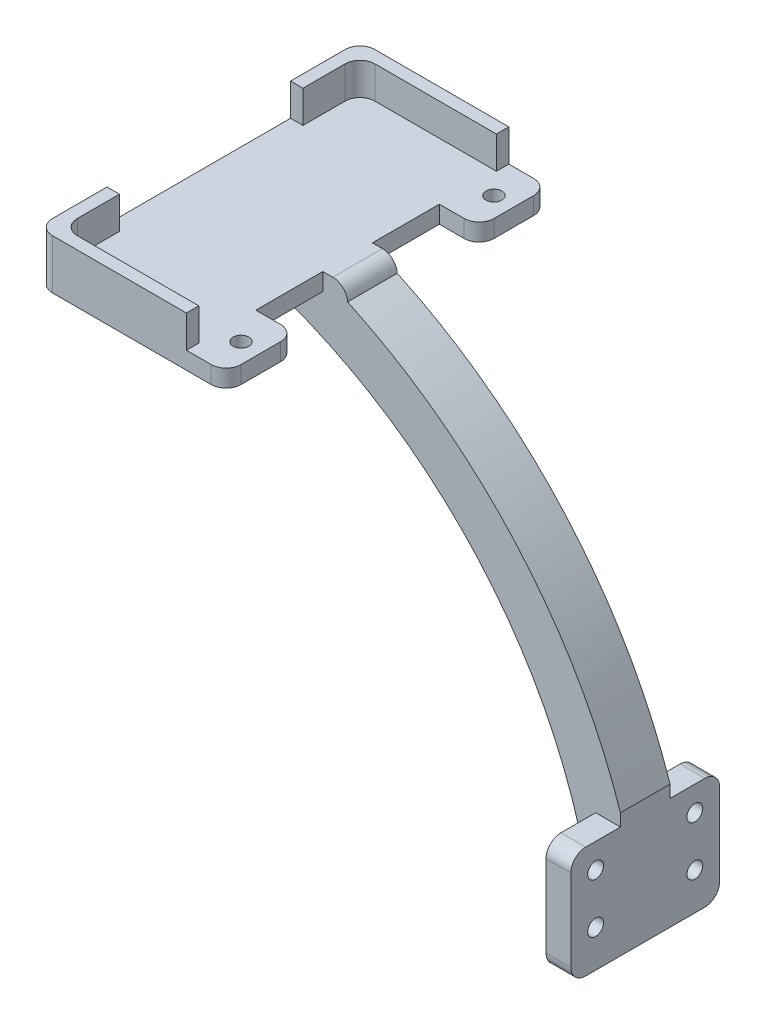
SolidWorks part; units mm, degrees
ref_plane "Plan de face" through (0, 0, 0) normal (0, 0, 1) x (1, 0, 0)
ref_plane "Plan de dessus" through (0, 0, 0) normal (0, 1, 0) x (1, 0, 0)
ref_plane "Plan de droite" through (0, 0, 0) normal (1, 0, 0) x (0, 0, -1)
sketch "Esquisse1" plane through (0, 0, 0) normal (0, 0, 1) x (1, 0, 0)
  line L1 (-15, -5) -> (15, -5)
  line L2 (-15, -5) -> (-15, 5)
  line L3 (-15, 5) -> (15, 5)
  line L4 (15, -5) -> (15, 5)
  line L5 (-15, -5) -> (15, 5) construction
  line L6 (-15, 5) -> (15, -5) construction
  point P0 (0, 0)
  dimension "D1" = 30
  dimension "D2" = 10
extrude "Boss.-Extru.1" add sketch "Esquisse1" along normal blind 65
sketch "Esquisse2" plane through (0, 5, 0) normal (0, 1, 0) x (1, 0, 0)
  line L0 (-15, -65) -> (-15, 0) construction
  line L1 (-15, -14) -> (-12.5, -14)
  line L2 (-15, -14) -> (-15, -51)
  line L3 (-15, -51) -> (-12.5, -51)
  line L5 (15, -65) -> (15, 0) construction
  line L6 (-12.5, -51) -> (-12.5, -62.5)
  line L7 (15, -2.5) -> (-12.5, -2.5)
  line L8 (15, -2.5) -> (15, -62.5)
  line L9 (15, -62.5) -> (-12.5, -62.5)
  line L10 (-12.5, -2.5) -> (-12.5, -14)
  point P6 (-15, -32.5)
  dimension "D1" = 37
  dimension "D2" = 2.5
  dimension "D3" = 60
extrude "Enlèv. mat.-Extru.1" cut sketch "Esquisse2" against normal blind 6.5
sketch "Esquisse3" plane through (15, 0, 0) normal (1, 0, 0) x (0, 0, -1)
  line L0 (-62.5, -1.5) -> (-2.5, -1.5) construction
  line L1 (-65, -5) -> (-51, -5)
  line L2 (-65, -5) -> (-65, -1.5)
  line L3 (-65, -1.5) -> (-51, -1.5)
  line L4 (-51, -5) -> (-51, -1.5)
  line L5 (-51, -1.5) -> (-62.5, -1.5) construction
  line L7 (-14, -1.5) -> (0, -1.5)
  line L8 (-14, -1.5) -> (-14, -5)
  line L9 (-14, -5) -> (0, -5)
  line L10 (0, -1.5) -> (0, -5)
extrude "Boss.-Extru.2" add sketch "Esquisse3" along normal blind 8
sketch "Esquisse4" plane through (0, -1.5, 0) normal (0, 1, 0) x (1, 0, 0)
  line L0 (19, -7) -> (19, -58) construction
  line L1 (-15, -14) -> (-15, -51) construction
  line L2 (23, 0) -> (23, -14) construction
  line L3 (23, 0) -> (15, 0) construction
  circle A0 centre (19, -7) radius 1.6
  circle A1 centre (19, -58) radius 1.6
  point P2 (19, -32.5)
  point P5 (-15, -32.5)
  point P8 (23, -7)
  point P11 (19, 0)
  dimension "D1" = 3.2
extrude "Enlèv. mat.-Extru.2" cut sketch "Esquisse4" against normal blind 4
fillet "Congé1" radius 3 6 edges at (-15, 0, 0) (-15, 0, 65) (23, -3.25, 65) (23, -3.25, 0) (23, -3.25, 14) (23, -3.25, 51)
sketch "Esquisse5" plane through (0, 0, 65) normal (0, 0, 1) x (1, 0, 0)
  line L0 (-15, -5) -> (75, -5) construction
  line L1 (75, -5) -> (75, -66) construction
  line L3 (75, -66) -> (70, -66) construction
  line L4 (75, -66) -> (75, -91)
  line L5 (75, -91) -> (70, -91)
  line L6 (70, -66) -> (70, -91) construction
  line L7 (20, -1.5) -> (15, -1.5) construction
  line L8 (13.3674, -1.5) -> (15, -1.5)
  line L9 (15, -1.5) -> (15, 5) construction
  line L10 (15, -1.5) -> (-15, -5)
  circle A0 centre (-24.0415, -98.9422) radius 94.3763 construction
  circle A1 centre (-24.0415, -98.9422) radius 104.3763 construction
  arc A2 (70, -91) -> (-15, -5) centre (-24.0415, -98.9422) ccw
  arc A3 (75, -66) -> (13.3674, -1.5) centre (-24.0415, -98.9422) ccw
  line M4 (-12, 5) -> (-12, -5)
  line M5 (-12, -5) -> (20, -5)
  line M6 (20, -5) -> (20, -1.5)
  dimension "D5" = 10
  dimension "D1" = 90
  dimension "D2" = 61
  dimension "D3" = 5
  dimension "D4" = 25
extrude "Boss.-Extru.3" add sketch "Esquisse5" against normal blind 5 and the other way blind 5 from offset 32.5 contours L4 A3 L10 A2 L5 M6 M5 M4 region at (73.7504, -78.5, 65) offset against normal yes
sketch "Esquisse6" plane through (0, -5, 0) normal (0, 1, 0) x (1, 0, 0)
  line L1 (20, -27.5) -> (15, -27.5)
  line L2 (20, -27.5) -> (20, -37.5)
  line L3 (20, -37.5) -> (15, -37.5)
  line L4 (15, -27.5) -> (15, -37.5)
extrude "Boss.-Extru.4" add sketch "Esquisse6" along normal blind 3.5
sketch "Esquisse7" plane through (75, 0, 0) normal (1, 0, 0) x (0, 0, -1)
  line L0 (-37.5, -66) -> (-27.5, -66) construction
  line L1 (-42.5, -83.5) -> (-22.5, -83.5) construction
  line L2 (-42.5, -83.5) -> (-42.5, -73.5) construction
  line L3 (-42.5, -73.5) -> (-22.5, -73.5) construction
  line L4 (-22.5, -83.5) -> (-22.5, -73.5) construction
  line L5 (-42.5, -83.5) -> (-22.5, -73.5) construction
  line L6 (-42.5, -73.5) -> (-22.5, -83.5) construction
  line L7 (-37.5, -91) -> (-27.5, -91) construction
  line L9 (-47.5, -91) -> (-17.5, -91)
  line L10 (-47.5, -91) -> (-47.5, -68.5)
  line L11 (-47.5, -68.5) -> (-17.5, -68.5)
  line L12 (-17.5, -91) -> (-17.5, -68.5)
  circle A0 centre (-42.5, -73.5) radius 1.6
  circle A1 centre (-22.5, -73.5) radius 1.6
  circle A2 centre (-22.5, -83.5) radius 1.6
  circle A3 centre (-42.5, -83.5) radius 1.6
  point P0 (-32.5, -78.5)
  point P8 (-32.5, -66)
  point P18 (-32.5, -91)
  dimension "D3" = 3.2
  dimension "D1" = 20
  dimension "D2" = 10
  dimension "D4" = 7.5
  dimension "D5" = 5
  dimension "D6" = 5
extrude "Boss.-Extru.5" add sketch "Esquisse7" against normal blind 5
sketch "Esquisse8" plane through (70, 0, 0) normal (1, 0, 0) x (0, 0, -1)
  line L1 (-40.8834, -70.7) -> (-44.1166, -70.7)
  line L2 (-44.1166, -70.7) -> (-45.7332, -73.5)
  line L3 (-45.7332, -73.5) -> (-44.1166, -76.3)
  line L4 (-44.1166, -76.3) -> (-40.8834, -76.3)
  line L5 (-40.8834, -76.3) -> (-39.2668, -73.5)
  line L6 (-39.2668, -73.5) -> (-40.8834, -70.7)
  line L7 (-20.8834, -70.7) -> (-24.1166, -70.7)
  line L8 (-24.1166, -70.7) -> (-25.7332, -73.5)
  line L9 (-25.7332, -73.5) -> (-24.1166, -76.3)
  line L10 (-24.1166, -76.3) -> (-20.8834, -76.3)
  line L11 (-20.8834, -76.3) -> (-19.2668, -73.5)
  line L12 (-19.2668, -73.5) -> (-20.8834, -70.7)
  line L13 (-20.8834, -86.3) -> (-19.2668, -83.5)
  line L14 (-19.2668, -83.5) -> (-20.8834, -80.7)
  line L15 (-20.8834, -80.7) -> (-24.1166, -80.7)
  line L16 (-24.1166, -80.7) -> (-25.7332, -83.5)
  line L17 (-25.7332, -83.5) -> (-24.1166, -86.3)
  line L18 (-24.1166, -86.3) -> (-20.8834, -86.3)
  line L19 (-40.8834, -86.3) -> (-39.2668, -83.5)
  line L20 (-39.2668, -83.5) -> (-40.8834, -80.7)
  line L21 (-40.8834, -80.7) -> (-44.1166, -80.7)
  line L22 (-44.1166, -80.7) -> (-45.7332, -83.5)
  line L23 (-45.7332, -83.5) -> (-44.1166, -86.3)
  line L24 (-44.1166, -86.3) -> (-40.8834, -86.3)
  circle A0 centre (-42.5, -73.5) radius 2.8 construction
  circle A1 centre (-22.5, -73.5) radius 2.8 construction
  circle A2 centre (-22.5, -83.5) radius 2.8 construction
  circle A3 centre (-42.5, -83.5) radius 2.8 construction
  dimension "D1" = 5.6
extrude "Enlèv. mat.-Extru.3" cut sketch "Esquisse8" along normal blind 2.5
fillet "Congé2" radius 3 4 edges at (72.5, -91, 17.5) (72.5, -91, 47.5) (72.5, -68.5, 47.5) (72.5, -68.5, 17.5)
fillet "Congé3" radius 3 1 edges at (20, -1.5, 32.5)
fillet "Congé4" radius 3 2 edges at (-12.5, 1.75, 2.5) (-12.5, 1.75, 62.5)
sketch "Esquisse9" plane through (0, 5, 0) normal (0, 1, 0) x (1, 0, 0)
  line L0 (15, -51) -> (15, -37.5) construction
  line L1 (49.7076, -78.7387) -> (-19.7076, -78.7387)
  line L2 (49.7076, -78.7387) -> (49.7076, -9.7613)
  line L3 (49.7076, -9.7613) -> (-19.7076, -9.7613)
  line L4 (-19.7076, -78.7387) -> (-19.7076, -9.7613)
  line L5 (49.7076, -78.7387) -> (-19.7076, -9.7613) construction
  line L6 (49.7076, -9.7613) -> (-19.7076, -78.7387) construction
  line L8 (42.5, -74.25) -> (-12.5, -74.25)
  line L9 (42.5, -74.25) -> (42.5, -14.25)
  line L10 (42.5, -14.25) -> (-12.5, -14.25)
  line L11 (-12.5, -74.25) -> (-12.5, -14.25)
  line L12 (42.5, -74.25) -> (-12.5, -14.25) construction
  line L13 (42.5, -14.25) -> (-12.5, -74.25) construction
  point P0 (15, -44.25)
  point P7 (15, -44.25)
  point P14 (-12.5, -2.5)
extrude "Enlèv. mat.-Extru.5" [suppressed] cut sketch "Esquisse9" against normal blind 6.5
